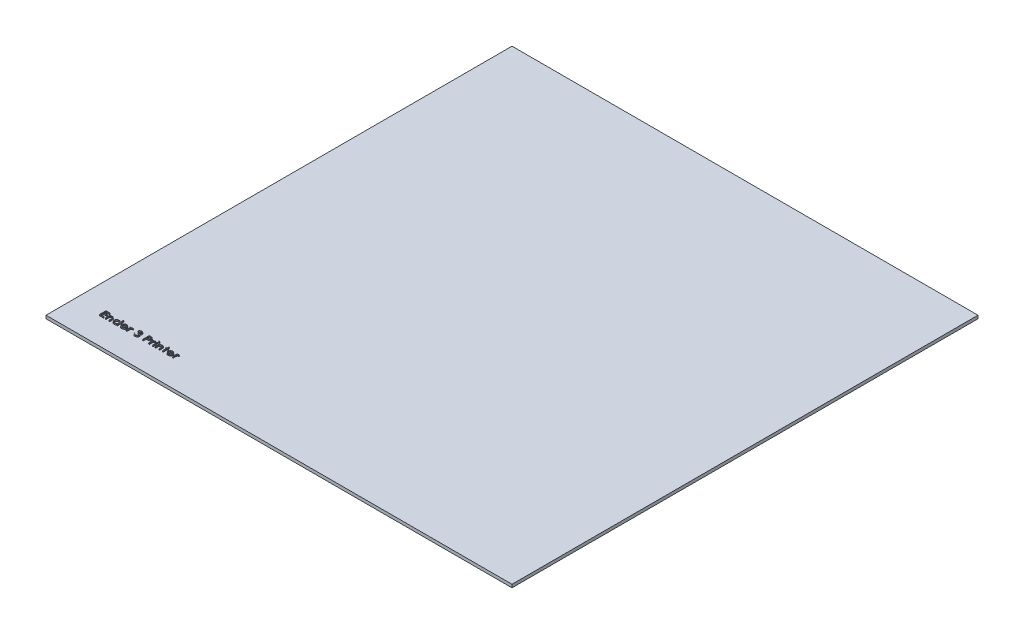
SolidWorks part; units mm, degrees
ref_plane "Front Plane" through (0, 0, 0) normal (0, 0, 1) x (1, 0, 0)
ref_plane "Top Plane" through (0, 0, 0) normal (0, 1, 0) x (1, 0, 0)
ref_plane "Right Plane" through (0, 0, 0) normal (1, 0, 0) x (0, 0, -1)
sketch "Sketch1" plane through (0, 0, 0) normal (0, 0, 1) x (1, 0, 0)
  line L0 (-9.75, 0) -> (9.75, 0) construction
  line L1 (-9.75, -8.5) -> (-9.75, 8.5)
  line L2 (9.75, -8.5) -> (9.75, 8.5)
  line L3 (-11.25, -8.5) -> (-11.25, 8.5)
  line L4 (-11.25, -8.5) -> (-9.75, -8.5)
  line L6 (11.25, -8.5) -> (11.25, 8.5)
  line L8 (9.75, -8.5) -> (11.25, -8.5)
  line L9 (-11.25, 8.5) -> (-11.25, 10)
  line L10 (-11.25, 10) -> (11.25, 10)
  line L11 (11.25, 10) -> (11.25, 8.5)
  line L12 (-9.75, 8.5) -> (9.75, 8.5)
  point P4 (0, 0)
  point P8 (-9.75, 0)
  point P11 (9.75, 0)
  dimension "D1" = 19.5
  dimension "D2" = 17
  dimension "D3" = 17
  dimension "D6" = 1.5
  dimension "D4" = 1.5
  dimension "D5" = 1.5
extrude "Clamp" add sketch "Sketch1" along normal blind 10 and the other way blind 10
sketch "Sketch2" plane through (-9.75, 0, 0) normal (1, 0, 0) x (0, 0, -1)
  line L0 (10, -8.5) -> (-10, -8.5) construction
  line L1 (-10, -8.5) -> (-10, 10) construction
  line L2 (0, 0) -> (0, -4.3366) construction
  circle A0 centre (-6, -5.5) radius 1
  circle A1 centre (6, -5.5) radius 1
  dimension "D1" = 2
  dimension "D2" = 3
  dimension "D3" = 4
extrude "Wheel Nub" add sketch "Sketch2" along normal blind 5.08
mirror "Nub Mirror" about plane through (0, 0, 0) normal (1, 0, 0) of "Wheel Nub"
sketch "Sketch3" plane through (0, 10, 0) normal (0, 1, 0) x (1, 0, 0)
  line L2 (-112.5, -112.5) -> (112.5, -112.5)
  line L3 (-112.5, -112.5) -> (-112.5, 112.5)
  line L4 (-112.5, 112.5) -> (112.5, 112.5)
  line L5 (112.5, -112.5) -> (112.5, 112.5)
  line L6 (-112.5, -112.5) -> (112.5, 112.5) construction
  line L7 (-112.5, 112.5) -> (112.5, -112.5) construction
  point P0 (0, 0)
  dimension "D1" = 225
  dimension "D2" = 225
extrude "Bed" add sketch "Sketch3" along normal blind 1.5 separate body
fillet "Inner Fillet" radius 2.54 2 edges at (9.75, 8.5, 0) (-9.75, 8.5, 0)
chamfer "Bottom Chamfer" distance 0.254 angle 45 8 edges at (10.5, -8.5, -10) (9.75, -8.5, 0) (10.5, -8.5, 10) (11.25, -8.5, 0) (-10.5, -8.5, -10) (-11.25, -8.5, 0) (-10.5, -8.5, 10) (-9.75, -8.5, 0)
chamfer "Peg Chamfer" distance 0.254 angle 45 4 edges at (-9.75, -5.5, -5) (-9.75, -5.5, 5) (9.75, -6.5, -6) (9.75, -6.5, 6)
sketch "Sketch6" plane through (0, 11.5, 0) normal (0, 1, 0) x (1, 0, 0)
  line L0 (-112.5, 112.5) -> (-112.5, -112.5) construction
  line L1 (-112.5, -112.5) -> (112.5, -112.5) construction
  text T0 "Ender 3 Printer" font "Century Gothic" height 3.175
  dimension "D1" = 12.7
  dimension "D2" = 12.7
extrude "Boss-Extrude4" add sketch "Sketch6" along normal blind 0.5 separate body
